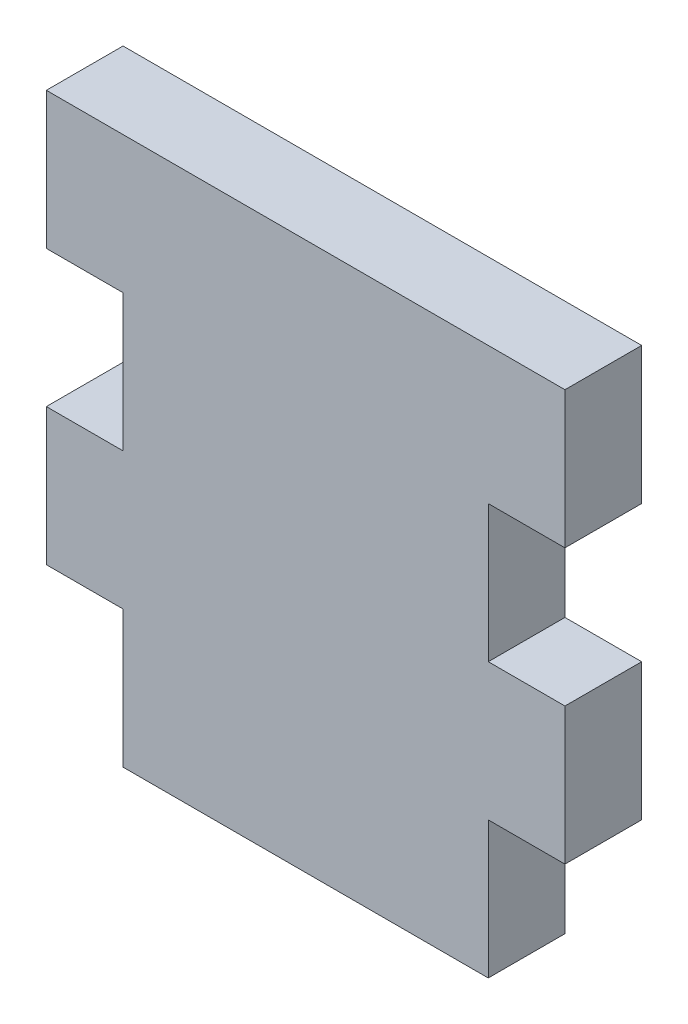
SolidWorks part; units mm, degrees
ref_plane "Front Plane" through (0, 0, 0) normal (0, 0, 1) x (1, 0, 0)
ref_plane "Top Plane" through (0, 0, 0) normal (0, 1, 0) x (1, 0, 0)
ref_plane "Right Plane" through (0, 0, 0) normal (1, 0, 0) x (0, 0, -1)
sketch "Sketch1" plane through (0, 0, 0) normal (0, 0, 1) x (1, 0, 0)
  line L1 (-88.0852, 14.1109) -> (-52.0172, 14.1109)
  line L2 (-88.0852, 14.1109) -> (-88.0852, -23.9891)
  line L3 (-88.0852, -23.9891) -> (-52.0172, -23.9891)
  line L4 (-52.0172, 14.1109) -> (-52.0172, -23.9891)
  dimension "D1" = 38.1
  dimension "D2" = 36.068
extrude "Boss-Extrude1" add sketch "Sketch1" along normal blind 5.334
sketch "Sketch2" plane through (0, 0, 5.334) normal (0, 0, 1) x (1, 0, 0)
  line L0 (-88.0852, 14.1109) -> (-88.0852, -23.9891) construction
  line L1 (-88.0852, -23.9891) -> (-82.7512, -23.9891)
  line L2 (-88.0852, -23.9891) -> (-88.0852, -14.4641)
  line L3 (-88.0852, -14.4641) -> (-82.7512, -14.4641)
  line L4 (-82.7512, -23.9891) -> (-82.7512, -14.4641)
  line L5 (-88.0852, -4.9391) -> (-82.7512, -4.9391)
  line L6 (-88.0852, -4.9391) -> (-88.0852, 4.5859)
  line L7 (-88.0852, 4.5859) -> (-82.7512, 4.5859)
  line L8 (-82.7512, -4.9391) -> (-82.7512, 4.5859)
  line L9 (-82.7512, 4.5859) -> (-82.7512, 14.1109) construction
  line L10 (-52.0172, 14.1109) -> (-88.0852, 14.1109) construction
  line L11 (-82.7512, -4.9391) -> (-82.7512, -14.4641) construction
  line L12 (-70.0512, 14.1109) -> (-70.0512, -23.9891) construction
  line L13 (-88.0852, -23.9891) -> (-52.0172, -23.9891) construction
  line L14 (-57.3512, -4.9391) -> (-57.3512, -14.4641) construction
  line L15 (-57.3512, 4.5859) -> (-57.3512, 14.1109) construction
  line L16 (-57.3512, -4.9391) -> (-57.3512, 4.5859)
  line L17 (-52.0172, 4.5859) -> (-57.3512, 4.5859)
  line L18 (-52.0172, -4.9391) -> (-52.0172, 4.5859)
  line L19 (-52.0172, -4.9391) -> (-57.3512, -4.9391)
  line L20 (-57.3512, -23.9891) -> (-57.3512, -14.4641)
  line L21 (-52.0172, -14.4641) -> (-57.3512, -14.4641)
  line L22 (-52.0172, -23.9891) -> (-52.0172, -14.4641)
  line L23 (-52.0172, -23.9891) -> (-57.3512, -23.9891)
  dimension "D1" = 5.334
extrude "Cut-Extrude1" cut sketch "Sketch2" against normal through all
equation "\"MDF\"= .21in"
equation "\"Foamcore\"= .13in"
equation "\"Gmaterial\"= \"MDF\""
equation "\"D1@Boss-Extrude1\"=\"MDF\""
equation "\"D1@Sketch2\"=\"MDF\""
equation "\"D2@Sketch1\"=\"MDF\"+\"MDF\"+1"
